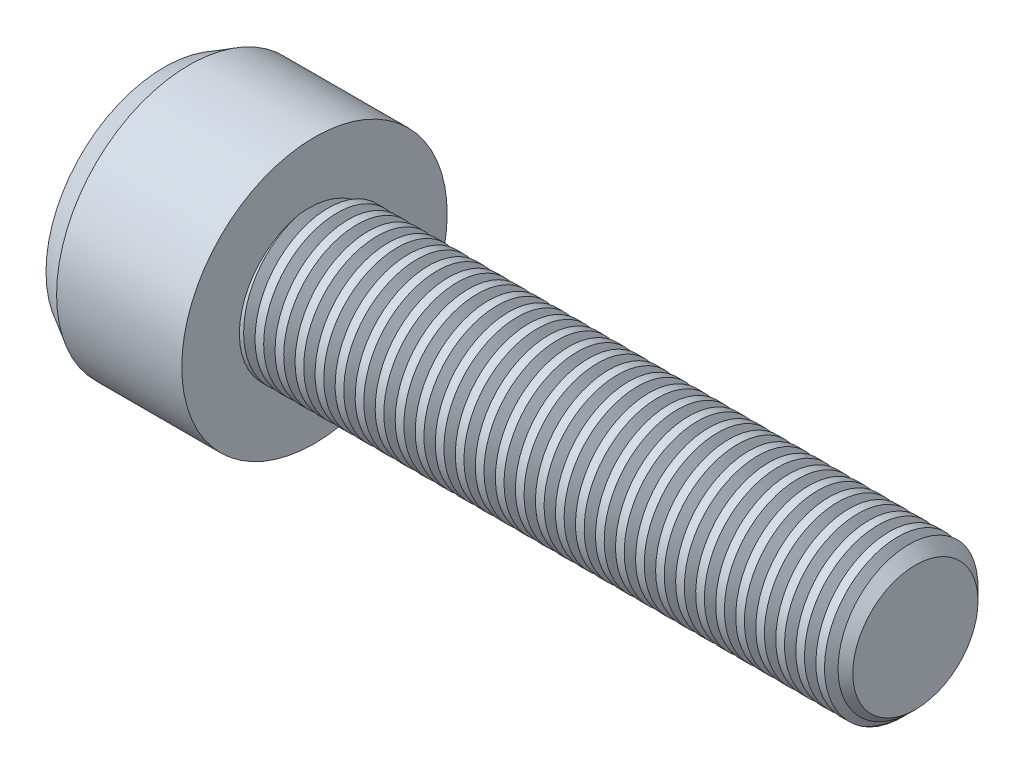
SolidWorks part; units mm, degrees
ref_plane "Front Plane" through (0, 0, 0) normal (0, 0, 1) x (1, 0, 0)
ref_plane "Top Plane" through (0, 0, 0) normal (0, 1, 0) x (1, 0, 0)
ref_plane "Right Plane" through (0, 0, 0) normal (1, 0, 0) x (0, 0, -1)
sketch "Sketch1" plane through (0, 0, 0) normal (1, 0, 0) x (0, 0, -1)
  circle A0 centre (0, 0) radius 2.65
  dimension "D1" = 5.3
extrude "Boss-Extrude4" add sketch "Sketch1" along normal blind 2.5
sketch "Sketch5" plane through (0, 0, 0) normal (-1, 0, 0) x (0, 0, 1)
  circle A0 centre (0, 0) radius 2.65
  circle A1 centre (0, 0) radius 2.65 construction
  dimension "D1" = 5.3
extrude "Boss-Extrude5" add sketch "Sketch5" along normal blind 0.5 draft 30
sketch "Sketch6" plane through (-0.5, 0, 0) normal (-1, 0, 0) x (0, 0, 1)
  line L1 (1.5011, 0) -> (0.7506, 1.3)
  line L2 (0.7506, 1.3) -> (-0.7506, 1.3)
  line L3 (-0.7506, 1.3) -> (-1.5011, 0)
  line L4 (-1.5011, 0) -> (-0.7506, -1.3)
  line L5 (-0.7506, -1.3) -> (0.7506, -1.3)
  line L6 (0.7506, -1.3) -> (1.5011, 0)
  circle A0 centre (0, 0) radius 1.3 construction
  circle A1 centre (0, 0) radius 2.3613 construction
  dimension "D1" = 2.6
extrude "Cut-Extrude5" cut sketch "Sketch6" against normal blind 1.5
sketch "Sketch7" plane through (1, 0, 0) normal (-1, 0, 0) x (0, 0, 1)
  line L0 (1.5011, 0) -> (0.7506, 1.3) construction
  line L1 (0.7506, 1.3) -> (-0.7506, 1.3)
  line L2 (-0.7506, 1.3) -> (-1.5011, 0)
  line L3 (-1.5011, 0) -> (-0.7506, -1.3)
  line L4 (-0.7506, -1.3) -> (0.7506, -1.3)
  line L5 (0.7506, -1.3) -> (1.5011, 0)
  line L6 (1.5011, 0) -> (0.7506, 1.3)
  line L7 (0.7506, 1.3) -> (-0.7506, 1.3) construction
  line L8 (0.7506, -1.3) -> (1.5011, 0) construction
  circle A0 centre (0, 0) radius 1.3 construction
extrude "Cut-Extrude11" cut sketch "Sketch7" against normal blind 0.25 draft 80
sketch "Sketch8" plane through (2.5, 0, 0) normal (1, 0, 0) x (0, 0, -1)
  circle A0 centre (0, 0) radius 1.5
  circle A1 centre (0, 0) radius 2.65 construction
  dimension "D1" = 3
extrude "Boss-Extrude8" add sketch "Sketch8" along normal blind 12
chamfer "Chamfer5" distance 0.25 angle 45 1 edges at (14.5, 0, -1.5)
sketch "Sketch12" plane through (14.5, 0, 0) normal (1, 0, 0) x (0, 0, -1)
  circle A0 centre (0, 0) radius 1.5
  circle A1 centre (0, 0) radius 1.25 construction
  dimension "D1" = 3
curve "Helix/Spiral1" pitch 0.4 height 12 turns 30
sketch "Sketch13" plane through (0, 0, 0) normal (0, 1, 0) x (1, 0, 0)
  line L1 (14.5, 1.3037) -> (14.67, 1.5981)
  line L2 (14.67, 1.5981) -> (14.33, 1.5981)
  line L3 (14.33, 1.5981) -> (14.5, 1.3037)
  dimension "D1" = 14.33
  dimension "D2" = 14.5
  dimension "D3" = 1.3037
sweep "Cut-Sweep1" cut profiles "Sketch13" path "Helix/Spiral1"
